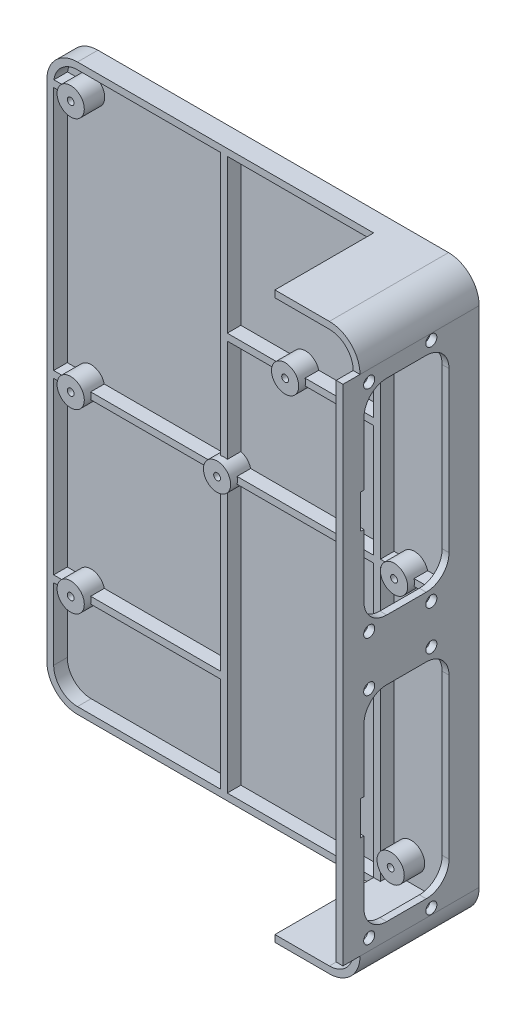
SolidWorks part; units mm, degrees
ref_plane "Front Plane" through (0, 0, 0) normal (0, 0, 1) x (1, 0, 0)
ref_plane "Top Plane" through (0, 0, 0) normal (0, 1, 0) x (1, 0, 0)
ref_plane "Right Plane" through (0, 0, 0) normal (1, 0, 0) x (0, 0, -1)
ref_plane "PCB BOTTOM SURFACE" through (0, 0, -1.6) normal (0, 0, 1) x (1, 0, 0)
ref_plane "CHASSIS FLOOR DATUM" through (0, 0, -7.6) normal (0, 0, 1) x (1, 0, 0)
ref_plane "RIB HEIGHT LIMIT" through (0, 0, -3.6) normal (0, 0, 1) x (1, 0, 0)
sketch "PCB PROFILE" plane through (0, 0, -1.6) normal (0, 0, 1) x (1, 0, 0)
  line L1 (4, 0) -> (107, 0)
  line L2 (0, 4) -> (0, 152)
  line L3 (4, 156) -> (107, 156)
  line L4 (111, 4) -> (111, 152)
  arc A0 (111, 4) -> (107, 0) centre (107, 4) cw
  arc A1 (111, 152) -> (107, 156) centre (107, 152) ccw
  arc A2 (4, 156) -> (0, 152) centre (4, 152) ccw
  arc A3 (0, 4) -> (4, 0) centre (4, 4) ccw
  point P7 (111, 0)
  point P12 (0, 156)
  point P15 (0, 0)
  dimension "D3" = 4
  dimension "D1" = 111
  dimension "D2" = 156
sketch "PCB SCREW HOLE LOCATIONS" plane through (0, 0, -1.6) normal (0, 0, 1) x (1, 0, 0)
  point P0 (4, 26)
  point P1 (98, 4)
  point P2 (99, 78)
  point P3 (47, 78)
  point P4 (4, 78)
  point P5 (4, 152)
  point P6 (98, 152)
  point P7 (67, 113)
  point P8 (0, 0)
  point P9 (0, 0)
  point P10 (0, 0)
  point P12 (0, 0)
  dimension "D1" = 26
  dimension "D2" = 4
  dimension "D3" = 78
  dimension "D4" = 152
  dimension "D5" = 47
  dimension "D6" = 98
  dimension "D7" = 99
  dimension "D8" = 4
  dimension "D9" = 113
  dimension "D10" = 67
sketch "Sketch2" plane through (0, 0, -1.6) normal (0, 0, 1) x (1, 0, 0)
  circle A0 centre (4, 26) radius 1
  circle A1 centre (4, 78) radius 1
  circle A2 centre (47, 78) radius 1
  circle A3 centre (67, 113) radius 1
  circle A4 centre (99, 78) radius 1
  circle A5 centre (98, 4) radius 1
  circle A6 centre (98, 152) radius 1
  circle A7 centre (4, 152) radius 1
  circle A8 centre (4, 26) radius 4
  circle A9 centre (4, 78) radius 4
  circle A10 centre (47, 78) radius 4
  circle A11 centre (67, 113) radius 4
  circle A12 centre (99, 78) radius 4
  circle A13 centre (98, 4) radius 4
  circle A14 centre (98, 152) radius 4
  circle A15 centre (4, 152) radius 4
  dimension "D1" = 2
  dimension "D2" = 3
extrude "SCREW BOSSES" add sketch "Sketch2" against normal up to surface (6 mm away) up to plane "CHASSIS FLOOR DATUM"
sketch "Sketch5" plane through (0, 0, -7.6) normal (0, 0, 1) x (1, 0, 0)
  line L4 (107, 161) -> (4, 161)
  line L5 (-5, 152) -> (-5, 4)
  line L6 (4, -5) -> (107, -5)
  line L7 (116, 4) -> (116, 152)
  line L8 (107, 159) -> (4, 159)
  line L9 (114, 4) -> (114, 152)
  line L10 (4, -3) -> (107, -3)
  line L11 (-3, 152) -> (-3, 4)
  line L12 (107, 159) -> (4, 159)
  line L13 (114, 4) -> (114, 152)
  line L14 (4, -3) -> (107, -3)
  line L15 (-3, 152) -> (-3, 4)
  arc A4 (4, 161) -> (-5, 152) centre (4, 152) ccw
  arc A5 (-5, 4) -> (4, -5) centre (4, 4) ccw
  arc A6 (107, -5) -> (116, 4) centre (107, 4) ccw
  arc A7 (116, 152) -> (107, 161) centre (107, 152) ccw
  arc A8 (114, 152) -> (107, 159) centre (107, 152) ccw
  arc A9 (107, -3) -> (114, 4) centre (107, 4) ccw
  arc A10 (-3, 4) -> (4, -3) centre (4, 4) ccw
  arc A11 (4, 159) -> (-3, 152) centre (4, 152) ccw
  arc A12 (114, 152) -> (107, 159) centre (107, 152) ccw
  arc A13 (107, -3) -> (114, 4) centre (107, 4) ccw
  arc A14 (-3, 4) -> (4, -3) centre (4, 4) ccw
  arc A15 (4, 159) -> (-3, 152) centre (4, 152) ccw
  dimension "D1" = 3
  dimension "D2" = 2
extrude "CHASSIS WALLS" add sketch "Sketch5" along normal up to surface (4 mm away) up to plane "RIB HEIGHT LIMIT"
sketch "Sketch3" plane through (0, 0, -7.6) normal (0, 0, 1) x (1, 0, 0)
  line L0 (5, 78) -> (46, 78)
  line L1 (48, 78) -> (98, 78)
  line L2 (47, 79) -> (47, 159)
  line L3 (47, 77) -> (47, -3)
  line L4 (92, 159) -> (92, -3)
  line L5 (5, 26) -> (47, 26)
  line L6 (3, 78) -> (-3, 78)
  line L7 (3, 26) -> (-3, 26)
  line L8 (3, 152) -> (-3, 152)
  line L9 (-3, 152) -> (-3, 4) construction
  line L10 (107, 159) -> (4, 159) construction
  line L11 (4, -3) -> (107, -3) construction
  line L12 (66, 113) -> (47, 113)
  line L13 (68, 113) -> (92, 113)
  line L14 (100, 78) -> (114, 78)
  line L15 (114, 4) -> (114, 152) construction
  circle A0 centre (4, 78) radius 1 construction
  circle A1 centre (47, 78) radius 1 construction
  circle A2 centre (99, 78) radius 1 construction
  circle A3 centre (4, 26) radius 1 construction
  circle A4 centre (4, 152) radius 1 construction
  circle A5 centre (67, 113) radius 1 construction
  dimension "D1" = 7
extrude "RIBBING" add sketch "Sketch3" along normal up to surface (4 mm away) thin up to plane "RIB HEIGHT LIMIT" thin type mid plane wall 2
sketch "Sketch6" plane through (0, 0, -7.6) normal (0, 0, 1) x (1, 0, 0)
  line L0 (4, -5) -> (107, -5) construction
  line L1 (116, 4) -> (116, 152) construction
  line L2 (107, 161) -> (4, 161) construction
  line L3 (-5, 152) -> (-5, 4) construction
  line L4 (4, -5) -> (107, -5)
  line L5 (116, 4) -> (116, 152)
  line L6 (107, 161) -> (4, 161)
  line L7 (-5, 152) -> (-5, 4)
  arc A0 (107, -5) -> (116, 4) centre (107, 4) ccw construction
  arc A1 (116, 152) -> (107, 161) centre (107, 152) ccw construction
  arc A2 (4, 161) -> (-5, 152) centre (4, 152) ccw construction
  arc A3 (-5, 4) -> (4, -5) centre (4, 4) ccw construction
  arc A4 (107, -5) -> (116, 4) centre (107, 4) ccw
  arc A5 (116, 152) -> (107, 161) centre (107, 152) ccw
  arc A6 (4, 161) -> (-5, 152) centre (4, 152) ccw
  arc A7 (-5, 4) -> (4, -5) centre (4, 4) ccw
extrude "CHASSIS FLOOR" add sketch "Sketch6" against normal blind 2
sketch "Sketch7" plane through (0, 0, -7.6) normal (0, 0, 1) x (1, 0, 0)
  line L0 (91, -3) -> (91, -5)
  line L1 (91, 161) -> (91, 159)
  line L2 (92, 159) -> (92, -3) construction
  line L4 (107, 161) -> (4, 161)
  line L5 (-5, 152) -> (-5, 4)
  line L6 (4, -5) -> (107, -5)
  line L7 (116, 4) -> (116, 152)
  line L8 (107, 161) -> (91, 161)
  line L10 (91, -5) -> (107, -5)
  line L11 (116, 4) -> (116, 152)
  line L12 (-3, 152) -> (-3, 4)
  line L13 (4, -3) -> (107, -3)
  line L14 (114, 4) -> (114, 152)
  line L15 (107, 159) -> (4, 159)
  line L17 (91, -3) -> (107, -3)
  line L18 (114, 4) -> (114, 152)
  line L19 (107, 159) -> (91, 159)
  arc A4 (4, 161) -> (-5, 152) centre (4, 152) ccw
  arc A5 (-5, 4) -> (4, -5) centre (4, 4) ccw
  arc A6 (107, -5) -> (116, 4) centre (107, 4) ccw
  arc A7 (116, 152) -> (107, 161) centre (107, 152) ccw
  arc A10 (107, -5) -> (116, 4) centre (107, 4) ccw
  arc A11 (116, 152) -> (107, 161) centre (107, 152) ccw
  arc A12 (-3, 4) -> (4, -3) centre (4, 4) ccw
  arc A13 (107, -3) -> (114, 4) centre (107, 4) ccw
  arc A14 (114, 152) -> (107, 159) centre (107, 152) ccw
  arc A15 (4, 159) -> (-3, 152) centre (4, 152) ccw
  arc A17 (107, -3) -> (114, 4) centre (107, 4) ccw
  arc A18 (114, 152) -> (107, 159) centre (107, 152) ccw
  dimension "D3" = 1
  dimension "D1" = 0
  dimension "D2" = 0
extrude "CONNECTOR FLANGE WALL" add sketch "Sketch7" along normal blind 38
sketch "Sketch9" plane through (0, 0, 30.4) normal (0, 0, 1) x (1, 0, 0)
  line L0 (114, 4) -> (116, 4)
  line L1 (114, 152) -> (116, 152)
  line L8 (107, 161) -> (91, 161)
  line L9 (91, 161) -> (91, 159)
  line L10 (91, 159) -> (107, 159)
  line L11 (114, 152) -> (114, 4)
  line L12 (107, -3) -> (91, -3)
  line L13 (91, -3) -> (91, -5)
  line L14 (91, -5) -> (107, -5)
  line L15 (116, 4) -> (116, 152)
  line L16 (107, 161) -> (91, 161)
  line L17 (91, 161) -> (91, 159)
  line L18 (91, 159) -> (107, 159)
  line L20 (107, -3) -> (91, -3)
  line L21 (91, -3) -> (91, -5)
  line L22 (91, -5) -> (107, -5)
  arc A4 (116, 152) -> (107, 161) centre (107, 152) ccw
  arc A5 (114, 152) -> (107, 159) centre (107, 152) ccw
  arc A6 (107, -3) -> (114, 4) centre (107, 4) ccw
  arc A7 (107, -5) -> (116, 4) centre (107, 4) ccw
  arc A8 (116, 152) -> (107, 161) centre (107, 152) ccw
  arc A9 (114, 152) -> (107, 159) centre (107, 152) ccw
  arc A10 (107, -3) -> (114, 4) centre (107, 4) ccw
  arc A11 (107, -5) -> (116, 4) centre (107, 4) ccw
  dimension "D1" = 0
extrude "CONNECTOR FLANGE WALL CUT FOR COVER MATING" cut sketch "Sketch9" against normal blind 5
sketch "Sketch8" plane through (116, 0, 0) normal (1, 0, 0) x (0, 0, -1)
  line L0 (-4.45, 72.2) -> (-4.45, 5.8) construction
  line L1 (-17.55, 69.125) -> (-5.95, 69.125)
  line L2 (-24.25, 62.425) -> (-24.25, 44)
  line L3 (-17.55, 8.875) -> (-5.95, 8.875)
  line L4 (0.75, 62.425) -> (0.75, 15.575)
  line L5 (-22.7, 7.3) -> (-22.7, 70.7) construction
  line L6 (-24.25, 44) -> (-25.25, 44)
  line L7 (-25.25, 44) -> (-25.25, 34)
  line L8 (-25.25, 34) -> (-24.25, 34)
  line L9 (-24.25, 34) -> (-24.25, 15.575)
  line L10 (-17.55, 147.125) -> (-5.95, 147.125)
  line L11 (-24.25, 140.425) -> (-24.25, 122)
  line L12 (0.75, 140.425) -> (0.75, 93.575)
  line L13 (-17.55, 86.875) -> (-5.95, 86.875)
  line L14 (-24.25, 112) -> (-24.25, 93.575)
  line L15 (-24.25, 122) -> (-25.25, 122)
  line L16 (-25.25, 122) -> (-25.25, 112)
  line L17 (-25.25, 112) -> (-24.25, 112)
  arc A0 (-24.25, 15.575) -> (-17.55, 8.875) centre (-17.55, 15.575) ccw
  arc A1 (0.75, 15.575) -> (-5.95, 8.875) centre (-5.95, 15.575) cw
  arc A2 (0.75, 62.425) -> (-5.95, 69.125) centre (-5.95, 62.425) ccw
  arc A3 (-17.55, 69.125) -> (-24.25, 62.425) centre (-17.55, 62.425) ccw
  circle A4 centre (-22.7, 7.3) radius 1.625
  circle A5 centre (-22.7, 70.7) radius 1.625
  circle A6 centre (-4.45, 72.2) radius 1.625
  circle A7 centre (-4.45, 5.8) radius 1.625
  circle A8 centre (-4.45, 150.2) radius 1.625
  circle A9 centre (-22.7, 148.7) radius 1.625
  arc A10 (-17.55, 147.125) -> (-24.25, 140.425) centre (-17.55, 140.425) ccw
  arc A11 (0.75, 140.425) -> (-5.95, 147.125) centre (-5.95, 140.425) ccw
  arc A12 (0.75, 93.575) -> (-5.95, 86.875) centre (-5.95, 93.575) cw
  arc A13 (-24.25, 93.575) -> (-17.55, 86.875) centre (-17.55, 93.575) ccw
  circle A14 centre (-22.7, 85.3) radius 1.625
  circle A15 centre (-4.45, 83.8) radius 1.625
  point P20 (-4.45, 39)
  point P21 (-22.7, 39)
  point P23 (0.75, 39)
  point P27 (-25.25, 39)
  point P29 (0.75, 117)
  dimension "D1" = 6.7
  dimension "D4" = 3.25
  dimension "D2" = 25
  dimension "D3" = 60.25
  dimension "D5" = 63.4
  dimension "D6" = 66.4
  dimension "D7" = 18.25
  dimension "D8" = 5.2
  dimension "D9" = 10
  dimension "D10" = 1
  dimension "D11" = 39
  dimension "D12" = 24.25
  dimension "D14" = 117
  dimension "D13" = 2
extrude "CONNECTOR CUTOUTS" cut sketch "Sketch8" against normal up to next
